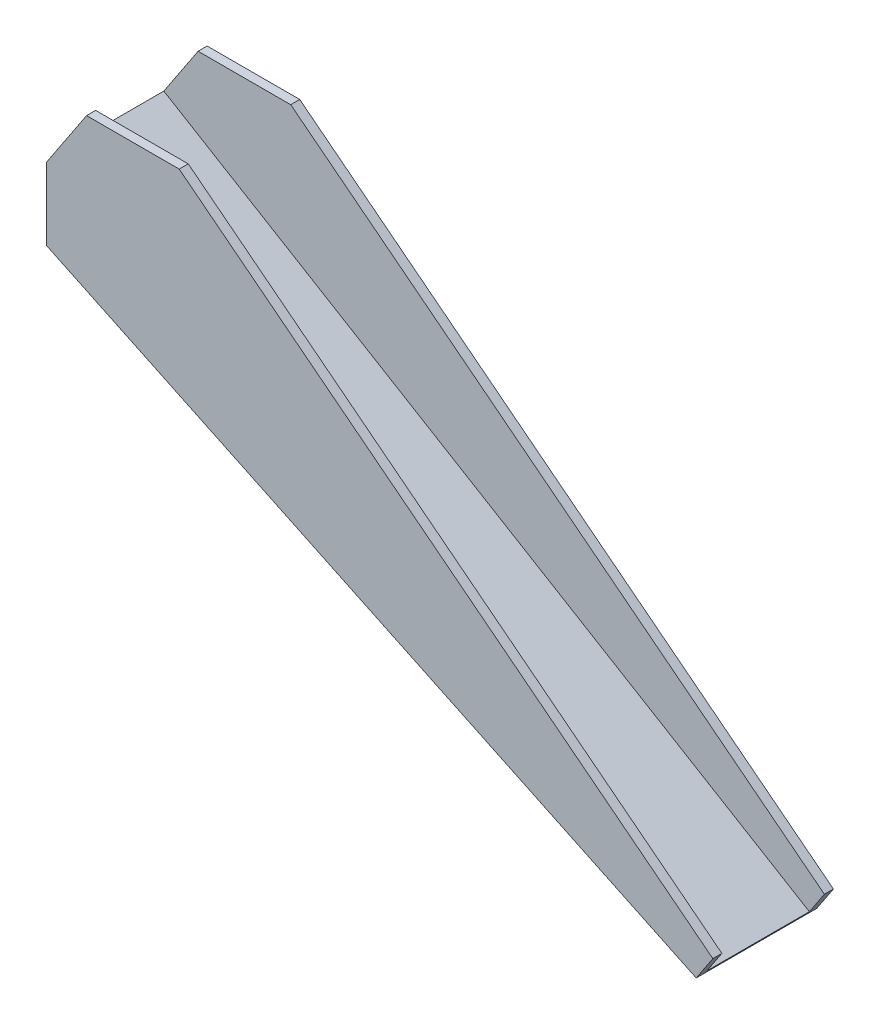
SolidWorks part; units mm, degrees
ref_plane "Plan de face" through (0, 0, 0) normal (0, 0, 1) x (1, 0, 0)
ref_plane "Plan de dessus" through (0, 0, 0) normal (0, 1, 0) x (1, 0, 0)
ref_plane "Plan de droite" through (0, 0, 0) normal (1, 0, 0) x (0, 0, -1)
sketch "Esquisse1" plane through (0, 0, 0) normal (0, 0, 1) x (1, 0, 0)
  line L1 (85.767, -38.3346) -> (88.5309, -34.1679)
  line L2 (88.5309, -34.1679) -> (0, 35)
  line L3 (-15.3668, 35) -> (-22, 25)
  line L4 (0, -57) -> (0, 41.1161) construction
  line L5 (0.3621, 0) -> (14.7069, 0) construction
  line L6 (-15.3668, 35) -> (0, 35)
  line L7 (85.767, -38.3346) -> (-22, 13)
  line L8 (-22, 25) -> (-22, 13)
  dimension "D1" = 125
  dimension "D2" = 52
  dimension "D3" = 22
  dimension "D4" = 25
  dimension "D5" = 5
  dimension "D6" = 12
  dimension "D7" = 35
  dimension "D8" = 12
extrude "Boss.-Extru.1" add sketch "Esquisse1" along normal mid plane 20
ref_plane "Plan1" through (5.8272, 9.6981, 0) normal (0.515, 0.8572, 0) x (0, 0, -1)
sketch "Esquisse3" plane through (5.8272, 9.6981, 0) normal (0.515, 0.8572, 0) x (0, 0, -1)
  line L0 (-10, -93.4835) -> (10, -93.4835) construction
  line L1 (-8.5, -93.4835) -> (8.5, -93.4835)
  line L2 (-8.5, -93.4835) -> (-8.5, 31.7336)
  line L3 (-8.5, 31.7336) -> (8.5, 31.7336)
  line L4 (8.5, -93.4835) -> (8.5, 31.7336)
  line L5 (-10, 31.7336) -> (10, 31.7336) construction
  line L6 (-10, -93.4835) -> (-10, 18.0263) construction
  line L7 (10, -93.4835) -> (10, 18.0263) construction
  dimension "D1" = 1.5
  dimension "D2" = 1.5
extrude "Enlèv. mat.-Extru.2" cut sketch "Esquisse3" along normal blind 20 from offset 0.5
sketch "Esquisse4" plane through (0, 1.5, 0) normal (0, 1, 0) x (1, 0, 0)
  line L0 (0.3621, -3.4812) -> (14.7069, -1.9893) construction
  line L1 (0.3621, 3.4812) -> (14.7069, 1.9893) construction
  line L2 (0.3621, -3.4812) -> (14.7069, -1.9893) construction
  line L3 (0.3621, 3.4812) -> (14.7069, 1.9893) construction
  line L4 (0.4138, 3.9785) -> (14.7586, 2.4866)
  line L5 (0.4138, -3.9785) -> (14.7586, -2.4866)
  arc A0 (14.7069, -1.9893) -> (14.7069, 1.9893) centre (14.5, 0) ccw construction
  arc A1 (0.3621, 3.4812) -> (0.3621, -3.4812) centre (0, 0) ccw construction
  arc A2 (14.7069, -1.9893) -> (14.7069, 1.9893) centre (14.5, 0) ccw construction
  arc A3 (0.3621, 3.4812) -> (0.3621, -3.4812) centre (0, 0) ccw construction
  arc A4 (14.7586, -2.4866) -> (14.7586, 2.4866) centre (14.5, 0) ccw
  arc A5 (0.4138, 3.9785) -> (0.4138, -3.9785) centre (0, 0) ccw
  dimension "D1" = 0.5
extrude "Enlèv. mat.-Extru.3" cut sketch "Esquisse4" against normal up to body
hole_wizard "Diamètre du perçage Ø5.0 (5)2" positions "Esquisse5" profile "Esquisse6" hole size "Ø5.0" standard "ISO" end condition up to next
sketch "Esquisse5" plane through (0, 1.5, 0) normal (0, -1, 0) x (-1, 0, 0)
  point P0 (0, 0)
sketch "Esquisse6" plane through (0, 1.5, 0) normal (1, 0, 0) x (0, 0, -1)
  line L0 (0, 0) -> (0, 12.2828)
  line L1 (0, 12.2828) -> (2.5, 12.2828)
  line L2 (2.5, 12.2828) -> (2.5, 0)
  line L5 (2.5, 0) -> (0, 0)
  line L11 (0, -6.35) -> (0, 107.95) construction
  dimension "Diamètre du perçage jusqu'au prochain" = 5
  dimension "Profondeur du perçage jusqu'au prochain" = 12.2828
hole_wizard "Diamètre du perçage Ø1.5 (1.5)1" positions "Esquisse7" profile "Esquisse8" hole size "Ø1.5" standard "ISO"
sketch "Esquisse7" plane through (0, 1.5, 0) normal (0, -1, 0) x (-1, 0, 0)
  point P0 (-14.5, 0)
  point P3 (-4.5, 0)
sketch "Esquisse8" plane through (14.5, 1.5, 0) normal (1, 0, 0) x (0, 0, -1)
  line L0 (0, 0) -> (0, 5.4506)
  line L1 (0, 5.4506) -> (0.75, 5)
  line L2 (0.75, 5) -> (0.75, 0)
  line L5 (0.75, 0) -> (0, 0)
  line L10 (0, 5.4506) -> (-0.75, 5) construction
  line L11 (0, -6.35) -> (0, 107.95) construction
  dimension "Diamètre du perçage" = 1.5
  dimension "Profondeur du perçage" = 5
  dimension "Angle de pointe" = 118
